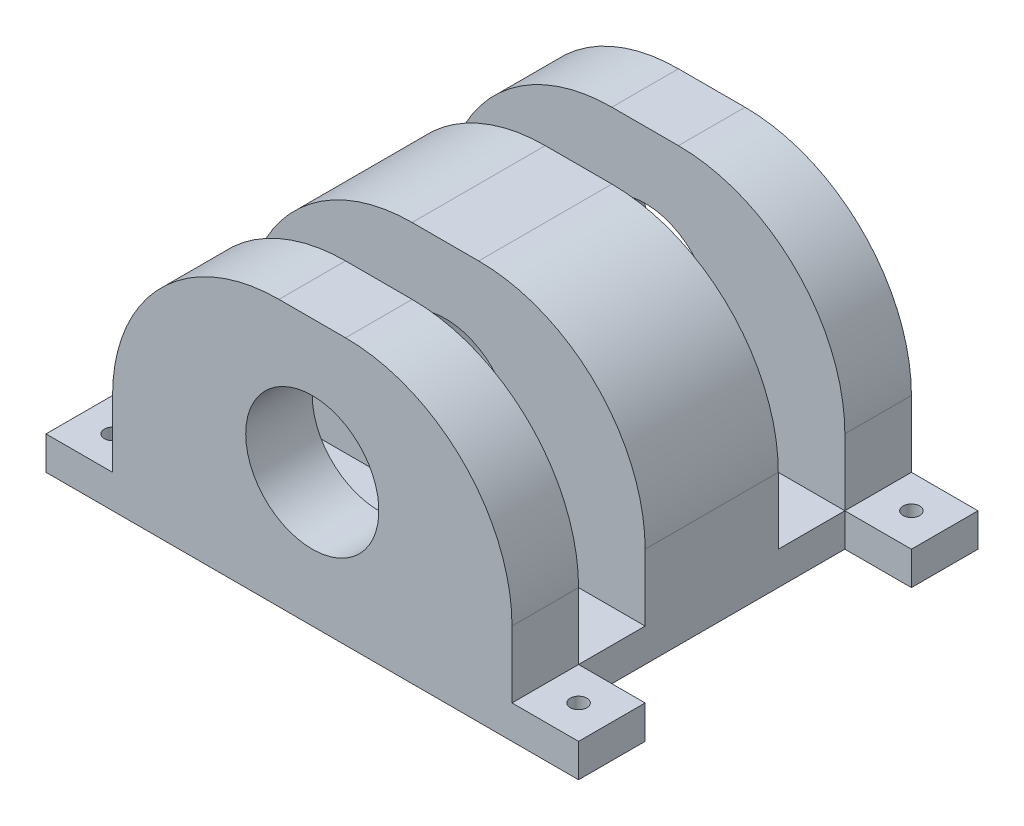
SolidWorks part; units mm, degrees
ref_plane "Front Plane" through (0, 0, 0) normal (0, 0, 1) x (1, 0, 0)
ref_plane "Top Plane" through (0, 0, 0) normal (0, 1, 0) x (1, 0, 0)
ref_plane "Right Plane" through (0, 0, 0) normal (1, 0, 0) x (0, 0, -1)
sketch "Sketch1" plane through (0, 0, 0) normal (0, 0, 1) x (1, 0, 0)
  line L1 (-76.2, -50.8) -> (76.2, -50.8)
  line L2 (-76.2, -38.1) -> (-76.2, -12.7)
  line L3 (-12.7, 50.8) -> (12.7, 50.8)
  line L4 (76.2, -38.1) -> (76.2, -12.7)
  line L5 (-76.2, -50.8) -> (76.2, 50.8) construction
  line L6 (-76.2, 50.8) -> (76.2, -50.8) construction
  line L7 (-76.2, -50.8) -> (-101.6, -50.8)
  line L9 (-76.2, -38.1) -> (-101.6, -38.1)
  line L10 (-101.6, -50.8) -> (-101.6, -38.1)
  line L11 (76.2, -50.8) -> (101.6, -50.8)
  line L13 (76.2, -38.1) -> (101.6, -38.1)
  line L14 (101.6, -50.8) -> (101.6, -38.1)
  arc A0 (76.2, -12.7) -> (12.7, 50.8) centre (12.7, -12.7) ccw
  arc A1 (-12.7, 50.8) -> (-76.2, -12.7) centre (-12.7, -12.7) ccw
  circle A2 centre (0, 0) radius 25.4
  point P0 (0, 0)
  dimension "D3" = 63.5
  dimension "D8" = 50.8
  dimension "D1" = 152.4
  dimension "D2" = 101.6
  dimension "D4" = 12.7
  dimension "D5" = 12.7
  dimension "D6" = 25.4
  dimension "D7" = 25.4
extrude "Boss-Extrude1" add sketch "Sketch1" along normal blind 152.4
sketch "Sketch3" plane through (0, 0, 0) normal (1, 0, 0) x (0, 0, -1)
  line L0 (-152.4, -38.1) -> (0, -38.1) construction
  line L1 (-127, -38.1) -> (-101.6, -38.1)
  line L2 (-127, -38.1) -> (-127, 50.8)
  line L3 (-127, 50.8) -> (-101.6, 50.8)
  line L4 (-101.6, -38.1) -> (-101.6, 50.8)
  line L5 (-152.4, 50.8) -> (0, 50.8) construction
  line L6 (-152.4, 50.8) -> (-152.4, -12.7) construction
  line L7 (-50.8, -38.1) -> (-25.4, -38.1)
  line L8 (-50.8, -38.1) -> (-50.8, 50.8)
  line L9 (-50.8, 50.8) -> (-25.4, 50.8)
  line L10 (-25.4, -38.1) -> (-25.4, 50.8)
  dimension "D1" = 25.4
  dimension "D2" = 25.4
  dimension "D3" = 50.8
  dimension "D4" = 25.4
extrude "Cut-Extrude1" cut sketch "Sketch3" against normal through all both and the other way through all
sketch "Sketch4" plane through (0, -38.1, 0) normal (0, 1, 0) x (1, 0, 0)
  line L0 (-101.6, -152.4) -> (-101.6, 0) construction
  line L1 (101.6, -152.4) -> (101.6, 0) construction
  line L2 (-76.2, 0) -> (-101.6, 0) construction
  line L3 (-76.2, -101.6) -> (-76.2, -50.8) construction
  line L4 (-101.6, -25.4) -> (-76.2, -25.4)
  line L5 (-101.6, -25.4) -> (-101.6, -127)
  line L6 (-101.6, -127) -> (-76.2, -127)
  line L7 (-76.2, -25.4) -> (-76.2, -127)
  line L8 (-76.2, -152.4) -> (-101.6, -152.4) construction
  line L9 (0, -55.88) -> (0, 55.88) construction
  line L10 (101.6, -127) -> (76.2, -127)
  line L11 (76.2, -25.4) -> (76.2, -127)
  line L12 (101.6, -25.4) -> (76.2, -25.4)
  line L13 (101.6, -25.4) -> (101.6, -127)
  point P0 (-88.9, -12.7)
  point P2 (-88.9, -139.7)
  point P3 (88.9, -12.7)
  point P5 (88.9, -139.7)
  dimension "D1" = 12.7
  dimension "D2" = 12.7
  dimension "D3" = 12.7
  dimension "D4" = 25.4
  dimension "D5" = 25.4
hole_wizard "1/4 (0.25) Diameter Hole1" positions "Sketch5" profile "Sketch6" hole size "1/4" standard "ANSI Inch" end condition through all
sketch "Sketch5" plane through (0, -38.1, 0) normal (0, 1, 0) x (1, 0, 0)
  point P3 (-88.9, -12.7)
  point P6 (-88.9, -139.7)
  point P9 (88.9, -12.7)
  point P15 (88.9, -139.7)
  point P18 (0, 0)
  point P19 (0, 0)
sketch "Sketch6" plane through (-88.9, -38.1, 12.7) normal (1, 0, 0) x (0, 0, 1)
  line L0 (0, 0) -> (0, 12.7)
  line L1 (0, 12.7) -> (3.175, 12.7)
  line L2 (3.175, 12.7) -> (3.175, 0)
  line L5 (3.175, 0) -> (0, 0)
  line L11 (0, -6.35) -> (0, 107.95) construction
  dimension "Thru Hole Dia." = 6.35
  dimension "Thru Hole Depth" = 12.7
extrude "Cut-Extrude2" cut sketch "Sketch4" against normal through all
